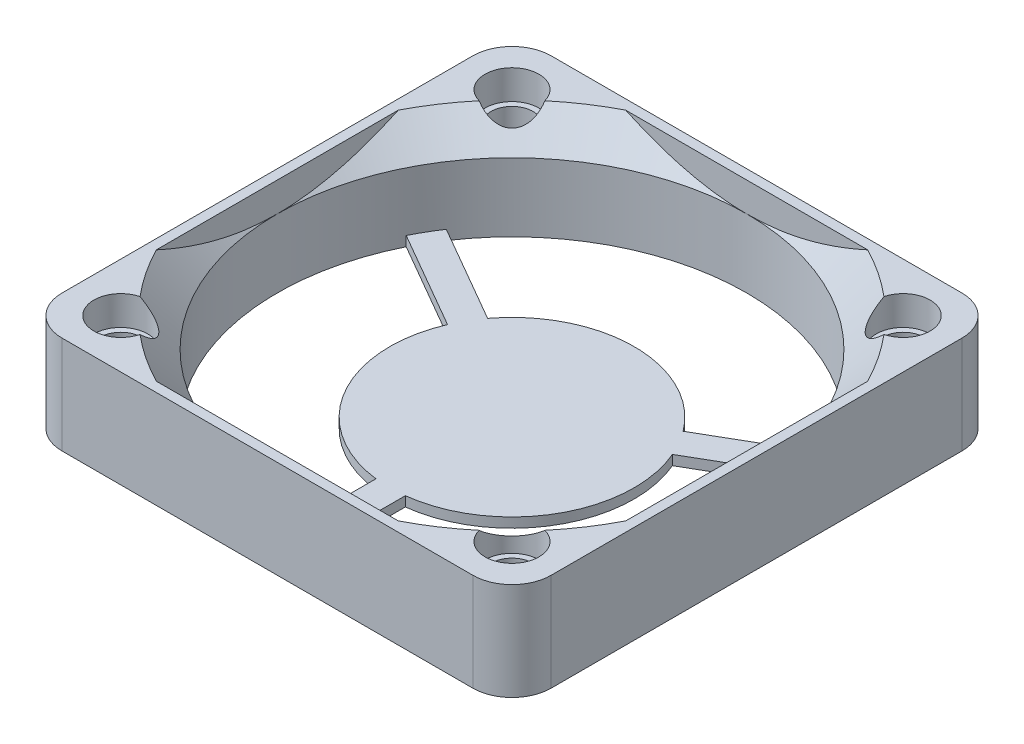
SolidWorks part; units mm, degrees
ref_plane "Front Plane" through (0, 0, 0) normal (0, 0, 1) x (1, 0, 0)
ref_plane "Top Plane" through (0, 0, 0) normal (0, 1, 0) x (1, 0, 0)
ref_plane "Right Plane" through (0, 0, 0) normal (1, 0, 0) x (0, 0, -1)
sketch "Sketch1" plane through (0, 0, 0) normal (0, 1, 0) x (1, 0, 0)
  line L1 (25, 25) -> (-25, 25)
  line L2 (25, 25) -> (25, -25)
  line L3 (25, -25) -> (-25, -25)
  line L4 (-25, 25) -> (-25, -25)
  line L5 (25, 25) -> (-25, -25) construction
  line L6 (25, -25) -> (-25, 25) construction
  circle A0 centre (0, 0) radius 24
  point P0 (0, 0)
  dimension "D3" = 48
  dimension "D1" = 50
  dimension "D2" = 50
extrude "Boss-Extrude1" add sketch "Sketch1" along normal blind 10
chamfer "Chamfer1" distance 3 angle 45 1 edges at (0, 10, 24)
sketch "Sketch4" plane through (0, 10, 0) normal (0, 1, 0) x (1, 0, 0)
  line L0 (-24, 24) -> (-24, -24)
  line L1 (25, 25) -> (-25, 25)
  line L2 (25, 25) -> (25, -25)
  line L3 (25, -25) -> (-25, -25)
  line L4 (-25, 25) -> (-25, -25)
  line L5 (25, 25) -> (-25, -25) construction
  line L6 (25, -25) -> (-25, 25) construction
  line L7 (24, -24) -> (-24, -24)
  line L8 (24, 24) -> (24, -24)
  line L9 (24, 24) -> (-24, 24)
  point P0 (0, 0)
  dimension "D1" = 1
extrude "Boss-Extrude2" add sketch "Sketch4" against normal up to surface (10 mm away) up to face at (0, 0, 0)
sketch "Sketch5" plane through (0, 10, 0) normal (0, 1, 0) x (1, 0, 0)
  circle A0 centre (-20, 20) radius 2.75
  circle A1 centre (20, 20) radius 2.75
  circle A2 centre (20, -20) radius 2.75
  circle A3 centre (-20, -20) radius 2.75
  point P0 (0, 0)
  point P11 (0, 0)
  dimension "D2" = 5.5
  dimension "D4" = 4
  dimension "D1" = 20
  dimension "D3" = 20
extrude "Cut-Extrude1" cut sketch "Sketch5" against normal blind 3
fillet "Fillet1" radius 4 4 edges at (25, 5, -25) (25, 5, 25) (-25, 5, 25) (-25, 5, -25)
sketch "Sketch6" plane through (0, 0, 0) normal (0, 1, 0) x (1, 0, 0)
  circle A0 centre (0, 0) radius 12.5
  point P3 (0, -12.5)
  point P8 (12.5, 0)
  dimension "D1" = 25
extrude "Boss-Extrude5" add sketch "Sketch6" along normal blind 1 separate body
sketch "Sketch7" plane through (0, 7, 0) normal (0, 1, 0) x (1, 0, 0)
  circle A1 centre (-20, -20) radius 2.15
  circle A2 centre (-20, 20) radius 2.15
  circle A3 centre (20, 20) radius 2.15
  circle A4 centre (20, -20) radius 2.15
  point P0 (0, 0)
  point P6 (0, 0)
  point P19 (0, 0)
  dimension "D1" = 4.3
  dimension "D2" = 4
extrude "Cut-Extrude2" cut sketch "Sketch7" against normal blind 21
sketch "Sketch9" plane through (0, 0, 0) normal (0, -1, 0) x (1, 0, 0)
  line L1 (-1.5, 0.5) -> (1.5, 0.5)
  line L2 (-1.5, 0.5) -> (-1.5, 24.5)
  line L3 (-1.5, 24.5) -> (1.5, 24.5)
  line L4 (1.5, 0.5) -> (1.5, 24.5)
  line L5 (-1.5, 0.5) -> (1.5, 24.5) construction
  line L6 (-1.5, 24.5) -> (1.5, 0.5) construction
  circle A0 centre (0, 0) radius 12.5 construction
  point P0 (0, 12.5)
  dimension "D1" = 24
  dimension "D2" = 3
  dimension "D3" = 0
extrude "Boss-Extrude6" add sketch "Sketch9" against normal blind 1
pattern_circular "CirPattern1" count 3 over 360 about axis through (0, 0, 0) along (0, 1, 0) of "Boss-Extrude6"
